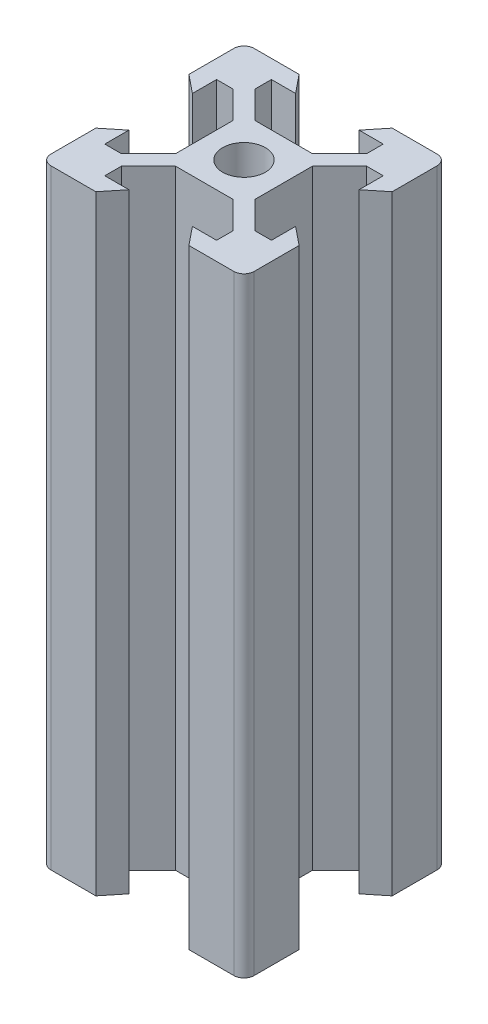
SolidWorks part; units mm, degrees
ref_plane "Front Plane" through (0, 0, 0) normal (0, 0, 1) x (1, 0, 0)
ref_plane "Top Plane" through (0, 0, 0) normal (0, 1, 0) x (1, 0, 0)
ref_plane "Right Plane" through (0, 0, 0) normal (1, 0, 0) x (0, 0, -1)
sketch "Sketch1" plane through (0, 0, 0) normal (0, 1, 0) x (1, 0, 0)
  line L0 (-3.125, 8.2) -> (-4.58, 10)
  line L1 (-9, 10) -> (9, 10)
  line L2 (-10, 9) -> (-10, -9)
  line L3 (-9, -10) -> (9, -10)
  line L4 (10, 9) -> (10, -9)
  line L5 (-10, 10) -> (10, -10) construction
  line L6 (-10, -10) -> (10, 10) construction
  line L7 (-10, 0) -> (0, 0) construction
  line L8 (0, 10) -> (0, 0) construction
  line L9 (-8.2, 3.125) -> (-10, 4.58)
  line L10 (-8.2, 3.125) -> (-8.2, 5.5)
  line L11 (-3.125, 8.2) -> (-5.5, 8.2)
  line L12 (-5.5, 8.2) -> (-5.5, 6.56)
  line L13 (-2.84, 3.9) -> (2.84, 3.9)
  line L14 (-5.5, 6.56) -> (-2.84, 3.9)
  line L15 (-8.2, 5.5) -> (-6.56, 5.5)
  line L16 (-6.56, 5.5) -> (-3.9, 2.84)
  line L17 (-3.9, 2.84) -> (-3.9, -2.84)
  line L18 (3.9, 2.84) -> (3.9, -2.84)
  line L19 (6.56, 5.5) -> (3.9, 2.84)
  line L20 (8.2, 5.5) -> (6.56, 5.5)
  line L21 (8.2, 3.125) -> (8.2, 5.5)
  line L22 (8.2, 3.125) -> (10, 4.58)
  line L23 (3.125, 8.2) -> (4.58, 10)
  line L24 (3.125, 8.2) -> (5.5, 8.2)
  line L25 (5.5, 8.2) -> (5.5, 6.56)
  line L26 (5.5, 6.56) -> (2.84, 3.9)
  line L27 (-8.2, -3.125) -> (-10, -4.58)
  line L28 (-8.2, -3.125) -> (-8.2, -5.5)
  line L29 (-8.2, -5.5) -> (-6.56, -5.5)
  line L30 (-6.56, -5.5) -> (-3.9, -2.84)
  line L31 (8.2, -3.125) -> (10, -4.58)
  line L32 (8.2, -3.125) -> (8.2, -5.5)
  line L33 (8.2, -5.5) -> (6.56, -5.5)
  line L34 (6.56, -5.5) -> (3.9, -2.84)
  line L35 (5.5, -6.56) -> (2.84, -3.9)
  line L36 (5.5, -8.2) -> (5.5, -6.56)
  line L37 (3.125, -8.2) -> (5.5, -8.2)
  line L38 (3.125, -8.2) -> (4.58, -10)
  line L39 (-5.5, -6.56) -> (-2.84, -3.9)
  line L40 (-2.84, -3.9) -> (2.84, -3.9)
  line L41 (-5.5, -8.2) -> (-5.5, -6.56)
  line L42 (-3.125, -8.2) -> (-5.5, -8.2)
  line L43 (-3.125, -8.2) -> (-4.58, -10)
  circle A0 centre (0, 0) radius 2.1
  arc A1 (-10, -9) -> (-9, -10) centre (-9, -9) ccw
  arc A2 (9, -10) -> (10, -9) centre (9, -9) ccw
  arc A3 (9, 10) -> (10, 9) centre (9, 9) cw
  arc A4 (-9, 10) -> (-10, 9) centre (-9, 9) ccw
  point P0 (0, 0)
  point P35 (0, 3.9)
  point P40 (-3.9, 0)
  point P41 (3.9, 0)
  dimension "D3" = 4.2
  dimension "D2" = 1
  dimension "D1" = 20
  dimension "D4" = 6.1
  dimension "D5" = 6.25
  dimension "D6" = 11
  dimension "D7" = 5.68
  dimension "D8" = 9.16
  dimension "D9" = 1.8
extrude "Boss-Extrude1" add sketch "Sketch1" along normal blind 60 contours L43 L42 L41 L39 L40 L35 L36 L37 L38 L3 L4 L31 L32 L33 L34 L18 L19 L20 L21 L22 L1 L23 L24 L25 L26 L13 L14 L12 L11 L0 L2 L9 L10 L15 L16 L17 L30 L29 L28 L27 A0 region at (-4.3125, 0, -8.4828)
